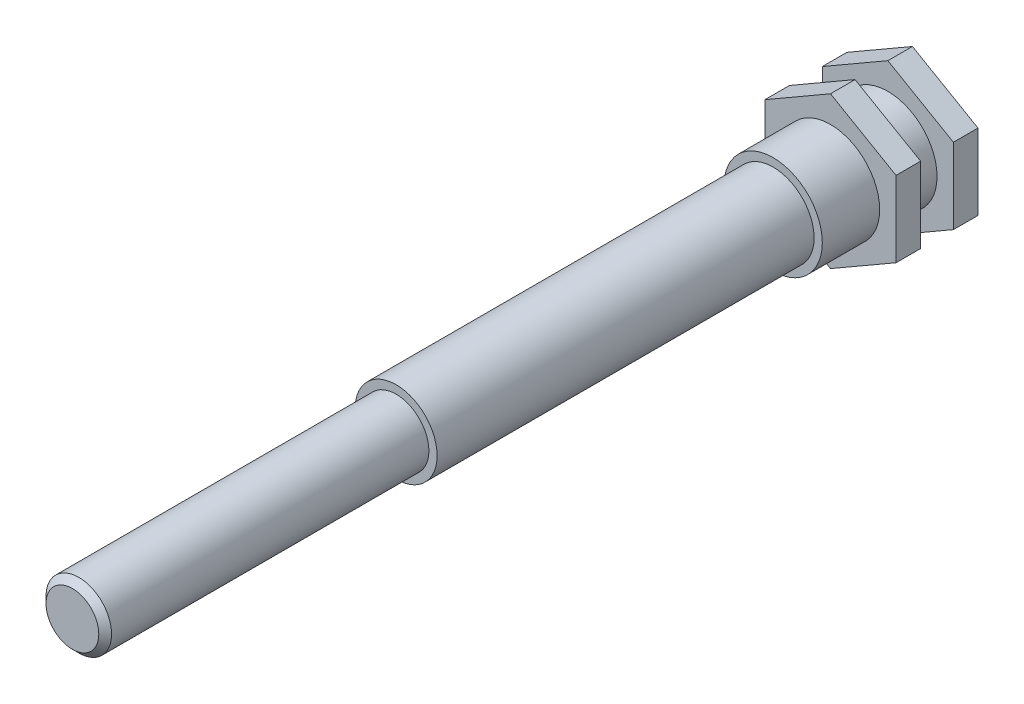
SolidWorks part; units mm, degrees
material "ЛC 59-1 ГОСТ 15527-70"
ref_plane "Спереди" through (0, 0, 0) normal (0, 0, 1) x (1, 0, 0)
ref_plane "Сверху" through (0, 0, 0) normal (0, 1, 0) x (1, 0, 0)
ref_plane "Справа" through (0, 0, 0) normal (1, 0, 0) x (0, 0, -1)
sketch "Эскиз1" plane through (0, 0, 0) normal (0, 0, 1) x (1, 0, 0)
  line L1 (-4, 2.3094) -> (-4, -2.3094)
  line L2 (-4, -2.3094) -> (0, -4.6188)
  line L3 (0, -4.6188) -> (4, -2.3094)
  line L4 (4, -2.3094) -> (4, 2.3094)
  line L5 (4, 2.3094) -> (0, 4.6188)
  line L6 (0, 4.6188) -> (-4, 2.3094)
  circle A0 centre (0, 0) radius 4 construction
  dimension "D1" = 8
extrude "Бобышка-Вытянуть1" add sketch "Эскиз1" along normal blind 1.5
sketch "Эскиз2" plane through (0, 0, 1.5) normal (0, 0, 1) x (1, 0, 0)
  circle A0 centre (0, 0) radius 3
  dimension "D1" = 6
extrude "Бобышка-Вытянуть2" add sketch "Эскиз2" along normal blind 7
extrude "Бобышка-Вытянуть3" add sketch "Эскиз1<2>" along normal blind 1.5 from offset 3.5
sketch "Эскиз1<2>" plane through (0, 0, 0) normal (0, 0, 1) x (1, 0, 0) same geometry as "Эскиз1"
sketch "Эскиз3" plane through (0, 0, 8.5) normal (0, 0, 1) x (1, 0, 0)
  circle A0 centre (0, 0) radius 2.5
  dimension "D1" = 5
extrude "Бобышка-Вытянуть4" add sketch "Эскиз3" along normal blind 23
sketch "Эскиз4" plane through (0, 0, 31.5) normal (0, 0, 1) x (1, 0, 0)
  circle A0 centre (0, 0) radius 2
  dimension "D1" = 4
extrude "Бобышка-Вытянуть5" add sketch "Эскиз4" along normal blind 19.75
cosmetic thread "Условное изображение резьбы1" parameters "D2"=3.22
chamfer "Фаска1" distance 0.39 angle 45 1 edges at (2, 0, 51.25)
